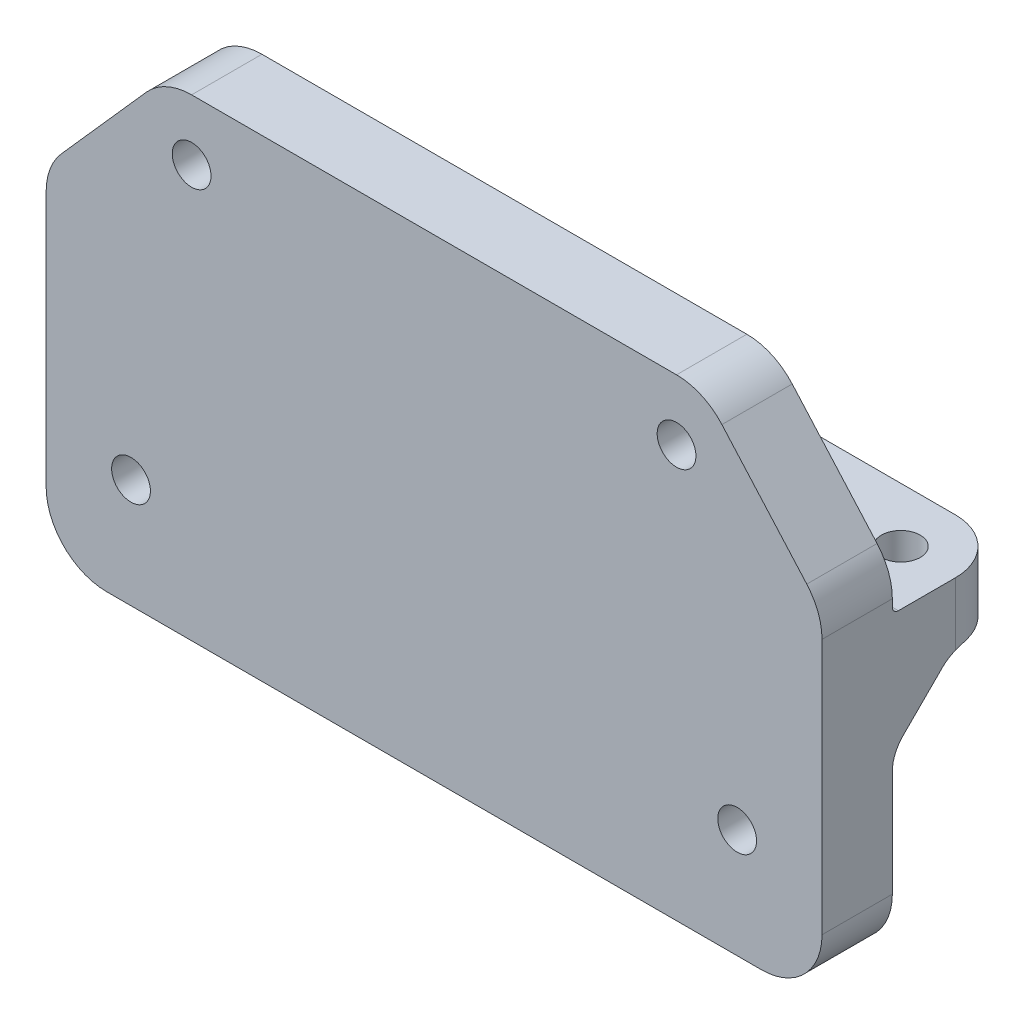
SolidWorks part; units mm, degrees
ref_plane "前视基准面" through (0, 0, 0) normal (0, 0, 1) x (1, 0, 0)
ref_plane "上视基准面" through (0, 0, 0) normal (0, 1, 0) x (1, 0, 0)
ref_plane "右视基准面" through (0, 0, 0) normal (1, 0, 0) x (0, 0, -1)
other "Configuration Table"
sketch "草图1" plane through (0, 0, 0) normal (0, 1, 0) x (1, 0, 0)
  line L0 (-27.5, 0) -> (0.8264, 0) construction
  line L1 (-32, -5) -> (32, -5) construction
  line L2 (-32, 0) -> (-32, -5)
  line L4 (-32, -5) -> (-32, -11)
  line L5 (-32, -11) -> (32, -11)
  line L6 (0, -11) -> (0, 0) construction
  line L7 (32, -5) -> (32, -11)
  line L8 (32, 0) -> (32, -5)
  line L9 (-27.5, 4.5) -> (27.5, 4.5)
  line L10 (0, 0) -> (27.5, 0) construction
  circle A0 centre (-27.5, 0) radius 1.6
  arc A1 (-27.5, 4.5) -> (-32, 0) centre (-27.5, 0) ccw
  arc A2 (27.5, 4.5) -> (32, 0) centre (27.5, 0) cw
  circle A3 centre (27.5, 0) radius 1.6
  point P5 (0.8264, 0)
  point P8 (0, -5)
  point P19 (0.2903, -0.1455)
  dimension "D1" = 3.2
  dimension "D4" = 9
  dimension "D2" = 5
  dimension "D3" = 55
  dimension "D5" = 6
extrude "凸台-拉伸1" add sketch "草图1" along normal blind 5
sketch "草图2" plane through (0, 5, 0) normal (0, 1, 0) x (1, 0, 0)
  line L0 (32, -11) -> (32, 0) construction
  line L1 (-32, -11) -> (32, -11)
  line L2 (-32, -11) -> (-32, -5.2)
  line L3 (-32, -5.2) -> (32, -5.2)
  line L4 (32, -11) -> (32, -5.2)
  circle A0 centre (27.5, 0) radius 1.6 construction
  dimension "D1" = 5.2
extrude "凸台-拉伸2" add sketch "草图2" along normal blind 3
sketch "草图3" plane through (0, 0, 11) normal (0, 0, 1) x (1, 0, 0)
  line L0 (-32, 8) -> (-22.2495, 19)
  line L1 (-32, 8) -> (32, 8) construction
  line L2 (-22.2495, 19) -> (22.2495, 19)
  line L3 (0, 19) -> (0, 0) construction
  line L4 (-32, 8) -> (32, 8)
  line L5 (32, 8) -> (22.2495, 19)
  line L6 (-32, 8) -> (-32, 0) construction
  circle A0 centre (-20, 14) radius 1.6
  circle A1 centre (20, 14) radius 1.6
  point P13 (0, 8)
  dimension "D3" = 3.2
  dimension "D1" = 40
  dimension "D2" = 6
  dimension "D4" = 5
  dimension "D5" = 5
extrude "凸台-拉伸3" add sketch "草图3" against normal up to surface (5.8 mm away) up to face at (0, 6.5, 5.2)
fillet "圆角1" radius 5 4 edges at (-32, 8, 8.1) (-22.2495, 19, 8.1) (22.2495, 19, 8.1) (32, 8, 8.1)
sketch "草图5" plane through (0, 0, 0) normal (1, 0, 0) x (0, 0, -1)
  line L5 (-11, 6.103) -> (-11, 0) construction
  line L6 (-11, 7) -> (-11, 3)
  line L8 (-11, 7) -> (-18, 7)
  line L9 (-18, 7) -> (-18, 0)
  line L10 (-18, 0) -> (-14, 0)
  line L11 (-14, 0) -> (-14, 3)
  line L12 (-14, 3) -> (-11, 3)
  line L13 (-11, 0) -> (0, 0) construction
  dimension "D1" = 3
  dimension "D2" = 4
  dimension "D3" = 4
  dimension "D4" = 7
extrude "凸台-拉伸4" [suppressed] add sketch "草图5" along normal mid plane 15
chamfer "倒角1" [suppressed] distance 2 angle 45
fillet "圆角4" [suppressed] radius 2
sketch "草图6" plane through (0, 0, 11) normal (0, 0, 1) x (1, 0, 0)
  line L0 (0, 0) -> (0, -21.2055) construction
  line L2 (-32, 0) -> (32, 0)
  line L3 (-32, 0) -> (-32, -20)
  line L4 (-32, -20) -> (32, -20)
  line L5 (32, 0) -> (32, -20)
  circle A0 centre (-25, -11) radius 1.6
  circle A1 centre (-20, 14) radius 1.6 construction
  circle A2 centre (25, -11) radius 1.6
  point P14 (32, 0)
  dimension "D1" = 25
  dimension "D3" = 3.2
  dimension "D2" = 50
  dimension "D4" = 20
extrude "凸台-拉伸5" add sketch "草图6" against normal up to surface (5.8 mm away) up to face at (0, 11.4712, 5.2)
sketch "草图4" plane through (0, 0, 5.2) normal (0, 0, -1) x (-1, 0, 0)
  circle A0 centre (-20, 14) radius 1.6 construction
  circle A1 centre (-20, 14) radius 1.6
  circle A2 centre (20, 14) radius 1.6 construction
  circle A3 centre (20, 14) radius 1.6
  circle A4 centre (-20, 14) radius 3.6
  circle A5 centre (20, 14) radius 3.6
  circle A6 centre (-25, -11) radius 3.6
  circle A7 centre (25, -11) radius 3.6
  dimension "D1" = 2
extrude "切除-拉伸1" cut sketch "草图4" against normal blind 3
fillet "圆角2" radius 0.5 1 edges at (0, 5, 5.2)
fillet "圆角5" radius 5 2 edges at (-32, -20, 8.1) (32, -20, 8.1)
sketch "草图7" plane through (0, 0, 0) normal (0, 1, 0) x (1, 0, 0)
  circle A0 centre (-27.5, 0) radius 3.5
  circle A1 centre (27.5, 0) radius 3.5
  dimension "D1" = 7
extrude "切除-拉伸2" cut sketch "草图7" along normal blind 2
chamfer "倒角4" distance 5 angle 45 1 edges at (0, 0, 5.2)
fillet "圆角7" radius 3 4 edges at (0, -5, 5.2) (-31.4971, 0, 0.2) (31.4971, 0, 0.2) (0, 0, 0.2)
